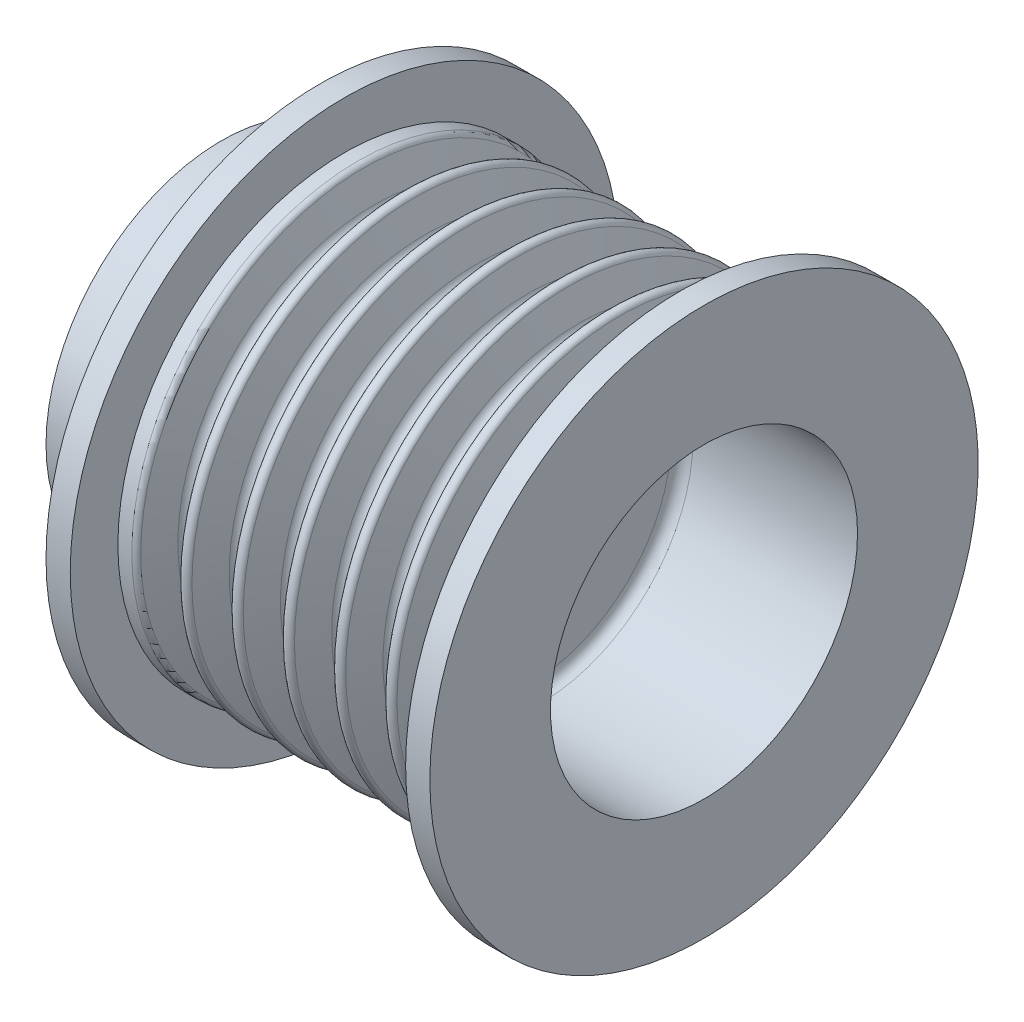
SolidWorks part; units mm, degrees
ref_plane "Front Plane" through (0, 0, 0) normal (0, 0, 1) x (1, 0, 0)
ref_plane "Top Plane" through (0, 0, 0) normal (0, 1, 0) x (1, 0, 0)
ref_plane "Right Plane" through (0, 0, 0) normal (1, 0, 0) x (0, 0, -1)
sketch "Sketch1" plane through (0, 0, 0) normal (0, 0, 1) x (1, 0, 0)
  line L4 (4.5, 12.5) -> (22, 12.5)
  line L5 (22, 12.5) -> (22, 4)
  line L10 (0, 0) -> (24, 0) construction
  line L12 (0, 4) -> (22, 4)
  line L13 (0, 4) -> (0, 8)
  line L14 (0, 8) -> (4.5, 8)
  line L15 (4.5, 8) -> (4.5, 12.5)
  dimension "D2" = 8
  dimension "D3" = 25
  dimension "D1" = 4.5
  dimension "D4" = 16
  dimension "D5" = 17.5
revolve "Revolve1" add sketch "Sketch1" angle 360 about L10
sketch "Sketch2" plane through (0, 0, 0) normal (0, 0, 1) x (1, 0, 0)
  line L0 (22, 0) -> (4.5, 0) construction
  line L1 (22, -12.5) -> (22, 12.5) construction
  line L3 (13.25, 0) -> (13.25, 12.5) construction
  line L4 (22, 12.5) -> (4.5, 12.5) construction
  line L5 (17.9236, 12.5) -> (20.2604, 12.5)
  line L6 (17.9236, 12.5) -> (17.9236, 10.3271)
  line L7 (20.2604, 12.5) -> (20.2604, 10.3271)
  line L8 (17.9236, 11.43) -> (20.2604, 11.43) construction
  line L9 (18.1623, 10.16) -> (18.6146, 8.9172)
  line L11 (19.5694, 8.9172) -> (20.0217, 10.16)
  line L12 (18.1623, 10.16) -> (20.0217, 10.16) construction
  line L13 (13.25, 12.5) -> (15.5868, 12.5) construction
  line L14 (15.5868, 12.5) -> (17.9236, 12.5) construction
  arc A0 (17.9236, 10.3271) -> (18.1623, 10.16) centre (17.9236, 10.0731) cw
  arc A1 (18.6146, 8.9172) -> (19.5694, 8.9172) centre (19.092, 9.0909) ccw
  arc A2 (20.2604, 10.3271) -> (20.0217, 10.16) centre (20.2604, 10.0731) ccw
  dimension "D3" = 0.254
  dimension "D6" = 0.508
  dimension "D1" = 2.3368
  dimension "D2" = 11.43
  dimension "D4" = 40
  dimension "D5" = 1.27
revolve "tooth groove" cut sketch "Sketch2" angle 360 about L0
pattern_linear "LPattern1" count 6 spacing 2.3368 along (-1, 0, 0) of "tooth groove"
sketch "Sketch3" plane through (0, 0, 0) normal (0, 0, 1) x (1, 0, 0)
  line L0 (22, 12.5) -> (20.2604, 12.5) construction
  line L2 (20.2604, 10.3271) -> (20.8954, 10.3271)
  line L4 (20.2604, 10.3271) -> (20.2604, 12.5)
  line L5 (20.2604, 12.5) -> (20.8954, 12.5)
  line L6 (20.8954, 10.3271) -> (20.8954, 12.5)
  line L7 (19.092, 8.5829) -> (19.092, 11.0958) construction
  line L8 (13.25, 10.3271) -> (13.25, 13.0355) construction
  line L9 (5.6046, 10.3271) -> (5.6046, 12.5)
  line L10 (6.2396, 12.5) -> (5.6046, 12.5)
  line L11 (6.2396, 10.3271) -> (6.2396, 12.5)
  line L12 (6.2396, 10.3271) -> (5.6046, 10.3271)
  line L13 (0, 0) -> (19.4427, 0) construction
  line L16 (20.2604, 10.3271) -> (20.2604, -10.3271) construction
  line L17 (20.2604, 10.3271) -> (20.2604, -10.3271) construction
  arc A3 (13.4887, 10.16) -> (13.0113, 10.16) centre (13.25, 10.0731) ccw construction
  arc A4 (18.6146, 8.9172) -> (19.5694, 8.9172) centre (19.092, 9.0909) ccw construction
  dimension "D1" = 1.8034
revolve "Cut-Revolve2" cut sketch "Sketch3" angle 360 about L13
sketch "Sketch5" plane through (22, 0, 0) normal (1, 0, 0) x (0, 0, -1)
  line L1 (1.5875, 2.4125) -> (-1.5875, 2.4125)
  line L2 (1.5875, 2.4125) -> (1.5875, 5.5875)
  line L3 (1.5875, 5.5875) -> (-1.5875, 5.5875)
  line L4 (-1.5875, 2.4125) -> (-1.5875, 5.5875)
  line L5 (1.5875, 2.4125) -> (-1.5875, 5.5875) construction
  line L6 (1.5875, 5.5875) -> (-1.5875, 2.4125) construction
  circle A0 centre (0, 0) radius 4 construction
  point P0 (0, 4)
  dimension "D1" = 3.175
  dimension "D2" = 3.175
extrude "keyway cut" cut sketch "Sketch5" against normal up to surface (22 mm away) contours L3 L4 L1 L2 up to face at (0, 0, 4)
sketch "Sketch6" plane through (22, 0, 0) normal (1, 0, 0) x (0, 0, -1)
  circle A0 centre (0, 0) radius 7
  dimension "D1" = 14
extrude "Cut-Extrude2" cut sketch "Sketch6" against normal blind 8
fillet "Fillet2" radius 0.5 1 edges at (14, 0, -7)
fillet "Fillet1" radius 1 1 edges at (4.5, 0, 8)
equation "\"D1@Sketch2\"=0.092in"
equation "\"D2@Sketch2\"=0.9in/2"
equation "\"D3@Sketch2\"=0.01in"
equation "\"D6@Sketch2\"=0.02in"
equation "\"D5@Sketch2\"=0.05in"
equation "\"D3@LPattern1\"=0.092in"
equation "\"D4@LPattern1\"=0.092in"
equation "\"D1@Sketch3\"=0.071in"
equation "\"D1@Sketch5\"=0.125in"
equation "\"D2@Sketch5\"=0.125in"
equation "\"D5@Sketch1\"=17.5"
